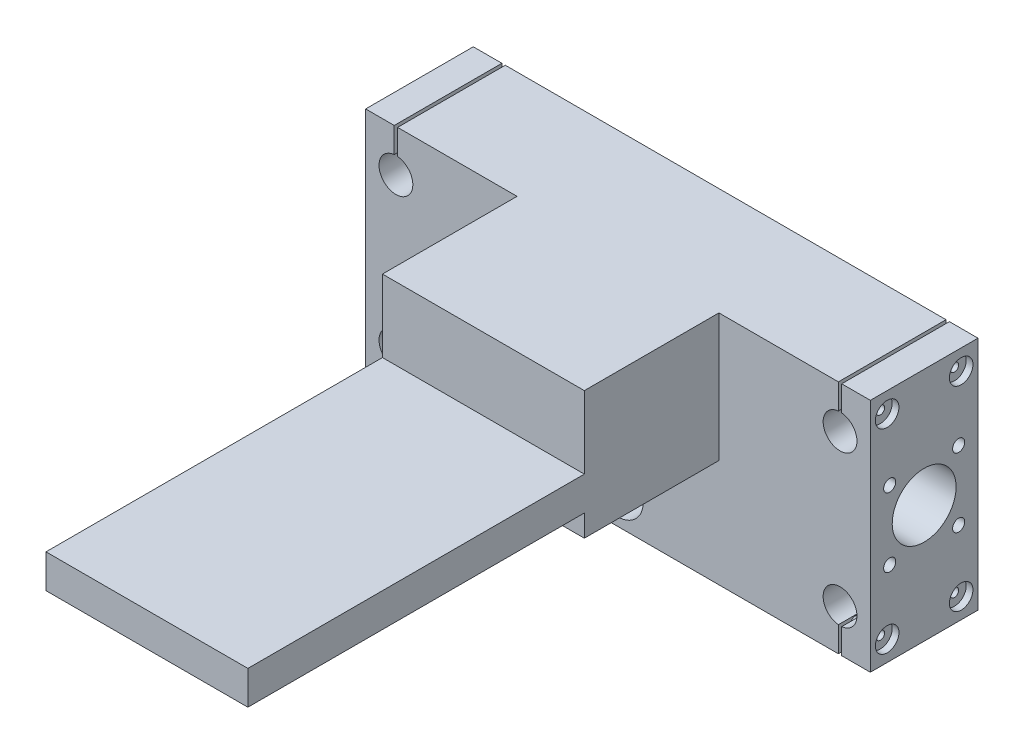
SolidWorks part; units mm, degrees
material "1060 Alloy"
ref_plane "Front Plane" through (0, 0, 0) normal (0, 0, 1) x (1, 0, 0)
ref_plane "Top Plane" through (0, 0, 0) normal (0, 1, 0) x (1, 0, 0)
ref_plane "Right Plane" through (0, 0, 0) normal (1, 0, 0) x (0, 0, -1)
sketch "Sketch1" plane through (0, 0, 0) normal (0, 0, 1) x (1, 0, 0)
  line L1 (-150, 0) -> (0, 0)
  line L2 (-150, 0) -> (-150, -70)
  line L3 (-150, -70) -> (0, -70)
  line L4 (0, 0) -> (0, -70)
  dimension "D1" = 150
  dimension "D2" = 70
extrude "Boss-Extrude1" add sketch "Sketch1" along normal blind 32
sketch "Sketch2" plane through (-150, 0, 0) normal (-1, 0, 0) x (0, 0, 1)
  line L0 (16, 0) -> (16, -70) construction
  line L1 (32, 0) -> (0, 0) construction
  line L2 (32, -70) -> (0, -70) construction
  line L3 (0, -35) -> (32, -35) construction
  line L4 (0, 0) -> (0, -70) construction
  line L5 (32, 0) -> (32, -70) construction
  circle A0 centre (16, -35) radius 9.5
  dimension "D1" = 19
extrude "Linear_bearing-cut-1" cut sketch "Sketch2" against normal blind 55
sketch "Sketch5" plane through (0, 0, 32) normal (0, 0, 1) x (1, 0, 0)
  line L0 (-75, 0) -> (-75, -70) construction
  line L1 (0, 0) -> (-150, 0) construction
  line L2 (-150, -70) -> (0, -70) construction
  line L3 (0, -35) -> (-150, -35) construction
  line L4 (0, -70) -> (0, 0) construction
  line L5 (-150, 0) -> (-150, -70) construction
  line L6 (-141, 0) -> (-141, -12.5) construction
  line L7 (-141, -12.5) -> (-9, -12.5) construction
  line L8 (-9, -12.5) -> (-9, 0) construction
  line L9 (-9, -57.5) -> (-9, -70) construction
  line L10 (-141, -57.5) -> (-9, -57.5) construction
  line L11 (-141, -70) -> (-141, -57.5) construction
  line L12 (-141.5, 0) -> (-141.5, -7.5)
  line L13 (-140.5, 0) -> (-140.5, -7.5)
  line L14 (-8.5, 0) -> (-8.5, -7.5)
  line L15 (-9.5, 0) -> (-9.5, -7.5)
  line L16 (-141.5, -70) -> (-141.5, -62.5)
  line L17 (-140.5, -70) -> (-140.5, -62.5)
  line L18 (-9.5, -70) -> (-9.5, -62.5)
  line L19 (-8.5, -70) -> (-8.5, -62.5)
  line L20 (-141.5, 0) -> (-140.5, 0)
  line L21 (-9.5, 0) -> (-8.5, 0)
  line L22 (-9.5, -70) -> (-8.5, -70)
  line L23 (-141.5, -70) -> (-140.5, -70)
  arc A0 (-141.5, -7.5) -> (-140.5, -7.5) centre (-141, -12.5) ccw
  arc A1 (-8.5, -7.5) -> (-9.5, -7.5) centre (-9, -12.5) cw
  arc A2 (-141.5, -62.5) -> (-140.5, -62.5) centre (-141, -57.5) cw
  arc A3 (-8.5, -62.5) -> (-9.5, -62.5) centre (-9, -57.5) ccw
  dimension "D1" = 9
  dimension "D3" = 12.5
  dimension "D5" = 0.5
  dimension "D6" = 7.5
extrude "Y-axis-shafts-cut" cut sketch "Sketch5" against normal through all
sketch "Sketch6" plane through (-95, 0, 0) normal (-1, 0, 0) x (0, 0, 1)
  line L0 (16, -25.5) -> (16, -44.5) construction
  circle A0 centre (16, -35) radius 9.5 construction
  circle A1 centre (16, -35) radius 9.5 construction
  circle A2 centre (16, -35) radius 6
  dimension "D1" = 12
sketch "Sketch7" plane through (0, 0, 0) normal (1, 0, 0) x (0, 0, -1)
  circle A0 centre (-16, -35) radius 9.5
  dimension "D1" = 19
extrude "Linear-bearing-cut-2" cut sketch "Sketch7" against normal blind 55
extrude "between-bearings" cut sketch "Sketch6" against normal through all
sketch "Sketch8" plane through (-150, 0, 0) normal (-1, 0, 0) x (0, 0, 1)
  line L0 (5, 0) -> (5, -6) construction
  line L1 (32, 0) -> (0, 0) construction
  line L2 (5, -6) -> (27, -6) construction
  line L3 (27, -6) -> (27, 0) construction
  line L4 (0, 0) -> (0, -70) construction
  line L5 (32, 0) -> (32, -70) construction
  line L6 (16, 0) -> (16, -70) construction
  line L7 (32, -70) -> (0, -70) construction
  line L8 (0, -35) -> (32, -35) construction
  line L9 (5, -39.9148) -> (4.7174, -39.9148) construction
  circle A0 centre (5, -6) radius 3.5
  circle A1 centre (27, -6) radius 3.5
  circle A2 centre (27, -64) radius 3.5
  circle A3 centre (5, -64) radius 3.5
  dimension "D4" = 7
  dimension "D1" = 5
  dimension "D3" = 6
extrude "shaft-holder-screw-cut" cut sketch "Sketch8" against normal blind 4
sketch "Sketch9" plane through (-146, 0, 0) normal (-1, 0, 0) x (0, 0, 1)
  line L0 (5, -2.5) -> (5, -9.5) construction
  line L1 (27, -2.5) -> (27, -9.5) construction
  line L2 (27, -60.5) -> (27, -67.5) construction
  line L3 (5, -60.5) -> (5, -67.5) construction
  circle A0 centre (5, -6) radius 3.5 construction
  circle A1 centre (5, -6) radius 3.5 construction
  circle A2 centre (27, -6) radius 3.5 construction
  circle A3 centre (27, -6) radius 3.5 construction
  circle A4 centre (27, -64) radius 3.5 construction
  circle A5 centre (27, -64) radius 3.5 construction
  circle A6 centre (5, -64) radius 3.5 construction
  circle A7 centre (5, -64) radius 3.5 construction
  circle A8 centre (5, -6) radius 1.25
  circle A9 centre (27, -6) radius 1.25
  circle A10 centre (5, -64) radius 1.25
  circle A11 centre (27, -64) radius 1.25
  dimension "D1" = 2.5
extrude "shaft-holder-screw-cut2" cut sketch "Sketch9" against normal blind 20
sketch "Sketch10" plane through (0, 0, 0) normal (1, 0, 0) x (0, 0, -1)
  line L0 (-27, 0) -> (-27, -6) construction
  line L1 (-32, 0) -> (0, 0) construction
  line L2 (-27, -6) -> (-5, -6) construction
  line L3 (-5, -6) -> (-5, 0) construction
  line L4 (-32, -70) -> (-32, 0) construction
  line L5 (0, -70) -> (0, 0) construction
  line L6 (-16, 0) -> (-16, -70) construction
  line L7 (-32, -70) -> (0, -70) construction
  line L8 (-32, -35) -> (0, -35) construction
  circle A0 centre (-27, -6) radius 3.5
  circle A1 centre (-5, -6) radius 3.5
  circle A2 centre (-5, -64) radius 3.5
  circle A3 centre (-27, -64) radius 3.5
  dimension "D4" = 7
  dimension "D1" = 5
  dimension "D2" = 6
extrude "shaft-holder-screw-cut-3" cut sketch "Sketch10" against normal blind 2
sketch "Sketch11" plane through (-2, 0, 0) normal (1, 0, 0) x (0, 0, -1)
  line L0 (-27, -2.5) -> (-27, -9.5) construction
  line L1 (-5, -2.5) -> (-5, -9.5) construction
  line L2 (-5, -60.5) -> (-5, -67.5) construction
  line L3 (-27, -60.5) -> (-27, -67.5) construction
  circle A0 centre (-27, -6) radius 3.5 construction
  circle A1 centre (-27, -6) radius 3.5 construction
  circle A2 centre (-5, -6) radius 3.5 construction
  circle A3 centre (-5, -6) radius 3.5 construction
  circle A4 centre (-5, -64) radius 3.5 construction
  circle A5 centre (-5, -64) radius 3.5 construction
  circle A6 centre (-27, -64) radius 3.5 construction
  circle A7 centre (-27, -64) radius 3.5 construction
  circle A8 centre (-27, -6) radius 1.25
  circle A9 centre (-5, -6) radius 1.25
  circle A10 centre (-5, -64) radius 1.25
  circle A11 centre (-27, -64) radius 1.25
  dimension "D1" = 2.5
extrude "shaft-holder-screw-cut-4" cut sketch "Sketch11" against normal blind 20
sketch "Sketch12" plane through (0, 0, 0) normal (1, 0, 0) x (0, 0, -1)
  line L0 (-5.75, 0) -> (-5.75, -24.75) construction
  line L1 (-32, 0) -> (0, 0) construction
  line L2 (-5.75, -24.75) -> (0, -24.75) construction
  line L3 (0, -70) -> (0, 0) construction
  line L4 (-16, 0) -> (-16, -70) construction
  line L5 (-32, -70) -> (0, -70) construction
  line L6 (0, -35) -> (-32, -35) construction
  line L7 (-32, -70) -> (-32, 0) construction
  circle A0 centre (-5.75, -24.75) radius 1.8
  circle A1 centre (-26.25, -24.75) radius 1.8
  circle A2 centre (-5.75, -45.25) radius 1.8
  circle A3 centre (-26.25, -45.25) radius 1.8
  dimension "D3" = 3.6
  dimension "D1" = 5.75
  dimension "D2" = 24.75
extrude "Linear-bearing-srew1" cut sketch "Sketch12" against normal blind 14
sketch "Sketch13" plane through (-150, 0, 0) normal (-1, 0, 0) x (0, 0, 1)
  line L0 (27.5, 0) -> (27.5, -24.75) construction
  line L1 (32, 0) -> (0, 0) construction
  line L2 (27.5, -24.75) -> (32, -24.75) construction
  line L3 (32, 0) -> (32, -70) construction
  line L4 (16, 0) -> (16, -70) construction
  line L5 (32, -70) -> (0, -70) construction
  line L6 (32, -35) -> (0, -35) construction
  line L7 (0, 0) -> (0, -70) construction
  circle A0 centre (27.5, -24.75) radius 1.85
  circle A1 centre (4.5, -24.75) radius 1.85
  circle A2 centre (27.5, -45.25) radius 1.85
  circle A3 centre (4.5, -45.25) radius 1.85
  dimension "D3" = 3.7
  dimension "D1" = 24.75
  dimension "D2" = 4.5
extrude "Linear-bearing-screw2" cut sketch "Sketch13" against normal blind 14
sketch "Sketch14" plane through (0, 0, 32) normal (0, 0, 1) x (1, 0, 0)
  line L1 (0, -70) -> (0, 0) construction
  line L2 (-140.5, -70) -> (-9.5, -70) construction
  circle A0 centre (-75, -60) radius 7.5
  dimension "D1" = 15
  dimension "D2" = 75
  dimension "D3" = 10
extrude "Cut-Extrude1" cut sketch "Sketch14" against normal through all
sketch "Sketch16" plane through (0, 0, 32) normal (0, 0, 1) x (1, 0, 0)
  line L0 (-9.5, 0) -> (-140.5, 0) construction
  line L1 (-105, 0) -> (-45, 0)
  line L2 (-105, 0) -> (-105, -38)
  line L3 (-105, -38) -> (-45, -38)
  line L4 (-45, 0) -> (-45, -38)
  line L5 (-75, -70) -> (-75, 0) construction
  line L6 (-140.5, -70) -> (-9.5, -70) construction
  point P10 (-75, 0)
  dimension "D1" = 38
  dimension "D2" = 60
extrude "Boss-Extrude3" add sketch "Sketch16" along normal blind 40
sketch "Sketch17" plane through (0, 0, 72) normal (0, 0, 1) x (1, 0, 0)
  line L0 (-105, 0) -> (-105, -38) construction
  line L1 (-105, -21.5) -> (-45, -21.5)
  line L2 (-105, -21.5) -> (-105, -31.5)
  line L3 (-105, -31.5) -> (-45, -31.5)
  line L4 (-45, -21.5) -> (-45, -31.5)
  line L5 (-45, -38) -> (-45, 0) construction
  line L6 (-45, 0) -> (-105, 0) construction
  dimension "D1" = 31.5
  dimension "D2" = 10
extrude "Boss-Extrude4" add sketch "Sketch17" along normal blind 100
